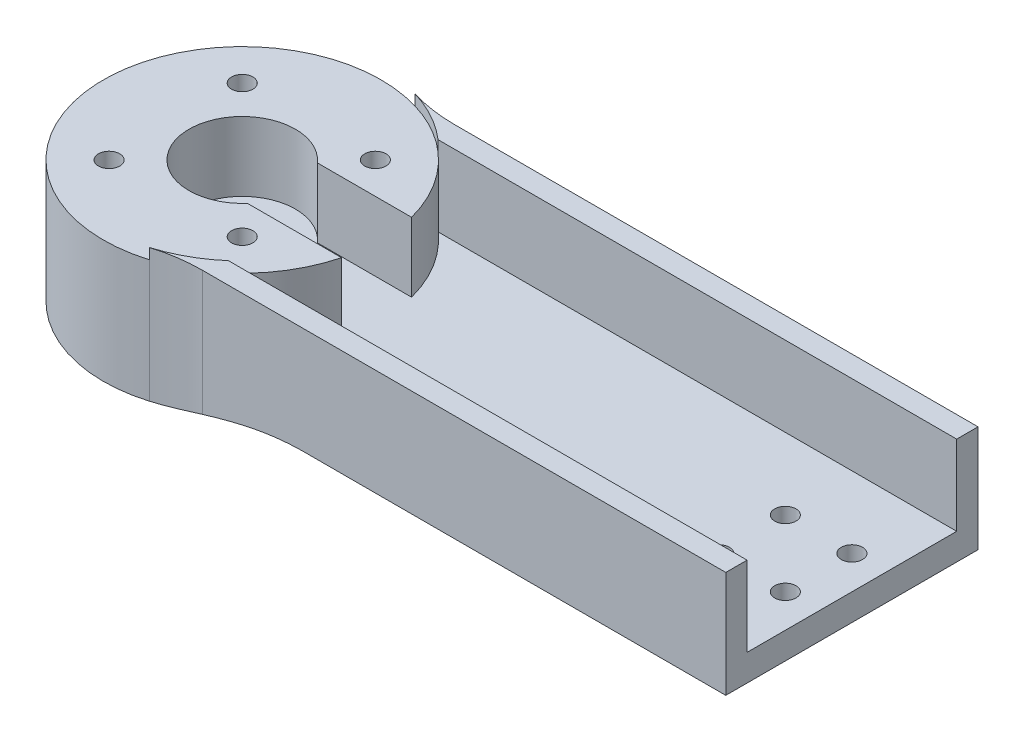
SolidWorks part; units mm, degrees
ref_plane "Front Plane" through (0, 0, 0) normal (0, 0, 1) x (1, 0, 0)
ref_plane "Top Plane" through (0, 0, 0) normal (0, 1, 0) x (1, 0, 0)
ref_plane "Right Plane" through (0, 0, 0) normal (1, 0, 0) x (0, 0, -1)
sketch "Sketch1" plane through (0, 0, 0) normal (0, 1, 0) x (1, 0, 0)
  line L1 (-50.3006, 19.6842) -> (50.3006, 19.6842)
  line L3 (-50.3006, -19.6842) -> (50.3006, -19.6842)
  line L5 (-50.3006, 19.6842) -> (50.3006, -19.6842) construction
  line L6 (-50.3006, -19.6842) -> (50.3006, 19.6842) construction
  line L9 (44.9237, -17.58) -> (39.4721, -17.58)
  line L11 (-50.3006, 0) -> (35, 0) construction
  line L12 (35, 0) -> (43.9443, 0) construction
  line L13 (39.4721, 0) -> (39.4721, -17.58) construction
  line L14 (39.4721, -8.79) -> (28.2221, -8.79) construction
  line L15 (50.3006, 19.6842) -> (50.3006, -19.6842)
  line L16 (-50.3006, 19.6842) -> (-50.3006, -19.6842) construction
  circle A0 centre (33.8471, -8.79) radius 2
  circle A1 centre (45.0971, -8.79) radius 2
  circle A2 centre (45.0971, 8.79) radius 2
  circle A3 centre (33.8471, 8.79) radius 2
  arc A6 (-50.3006, 19.6842) -> (-50.3006, -19.6842) centre (-61.1994, 0) ccw
  point P0 (0, 0)
  point P25 (-83.6994, 0)
  point P26 (50.3006, 0)
  dimension "D3" = 134
  dimension "D4" = 11.25
  dimension "D1" = 45
  dimension "D2" = 5.2035
extrude "Boss-Extrude2" add sketch "Sketch1" along normal blind 5
sketch "Sketch8" plane through (0, 5, 0) normal (0, 1, 0) x (1, 0, 0)
  line L0 (-50.3006, -19.6842) -> (50.3006, -19.6842) construction
  line L1 (-50.3006, 19.6842) -> (50.3006, 19.6842) construction
  line L2 (-50.3006, -19.6842) -> (50.3006, -19.6842)
  line L3 (-50.3006, 19.6842) -> (50.3006, 19.6842)
  line L4 (-50.3006, 23.6842) -> (50.3006, 23.6842)
  line L5 (-50.3006, -23.6842) -> (50.3006, -23.6842)
  line L6 (50.3006, 23.6842) -> (50.3006, 19.6842)
  line L7 (50.3006, -19.6842) -> (50.3006, -23.6842)
  line L8 (-50.3006, -19.6842) -> (-50.3006, -23.6842)
  line L9 (-50.3006, 23.6842) -> (-50.3006, 19.6842)
  dimension "D1" = 4
  dimension "D2" = 4
extrude "Boss-Extrude8" add sketch "Sketch8" along normal blind 15 and the other way up to surface other way up to face at (33.8471, 0, -6.79)
sketch "Sketch9" plane through (0, 5, 0) normal (0, 1, 0) x (1, 0, 0)
  circle A0 centre (-61.1994, 0) radius 26.0715
extrude "Boss-Extrude9" add sketch "Sketch9" along normal blind 15 and the other way blind 10
fillet "Fillet2" radius 30 3 edges at (-35.1279, 0, 0) (-50.3006, 10, -23.6842) (-50.3006, 10, 23.6842)
sketch "Sketch10" plane through (50.3006, 0, 0) normal (1, 0, 0) x (0, 0, -1)
  line L0 (-23.6842, 20) -> (-19.6842, 20) construction
  line L1 (-19.6842, 5) -> (-19.6842, 20) construction
  line L2 (19.6842, 5) -> (-19.6842, 5) construction
  line L3 (19.6842, 5) -> (19.6842, 20) construction
  line L4 (19.6842, 20) -> (23.6842, 20) construction
  line L5 (23.6842, 0) -> (23.6842, 20) construction
  line L6 (23.6842, 0) -> (-23.6842, 0) construction
  line L7 (-23.6842, 20) -> (-23.6842, -3.4498) construction
  line L8 (-23.6842, 20) -> (-19.6842, 20)
  line L9 (-19.6842, 5) -> (-19.6842, 20)
  line L10 (19.6842, 5) -> (-19.6842, 5)
  line L11 (19.6842, 5) -> (19.6842, 20)
  line L12 (19.6842, 20) -> (23.6842, 20)
  line L13 (23.6842, 0) -> (23.6842, 20)
  line L14 (23.6842, 0) -> (-23.6842, 0)
  line L15 (-23.6842, 20) -> (-23.6842, 0)
extrude "Boss-Extrude10" add sketch "Sketch10" along normal blind 3
sketch "Sketch11" plane through (0, 20, 0) normal (0, 1, 0) x (1, 0, 0)
  line L0 (-21.1994, 6.5745) -> (-53.6644, 6.5745)
  line L1 (-61.1994, 0) -> (0, 0) construction
  line L2 (-21.1994, -6.5745) -> (-53.6644, -6.5745)
  line L3 (-21.1994, 6.5745) -> (-21.1994, -6.5745)
  arc A0 (-53.6644, 6.5745) -> (-53.6644, -6.5745) centre (-61.1994, 0) ccw
  dimension "D1" = 40
  dimension "D2" = 20
extrude "Cut-Extrude3" cut sketch "Sketch11" against normal up to surface (15 mm away) up to face at (6.8424, 5, 0)
sketch "Sketch12" plane through (0, 20, 0) normal (0, 1, 0) x (1, 0, 0)
  line L5 (-73.6994, 12.5) -> (-48.6994, -12.5) construction
  line L6 (-73.6994, -12.5) -> (-48.6994, 12.5) construction
  line L7 (-73.6994, 12.5) -> (-48.6994, 12.5) construction
  line L9 (-73.6994, -12.5) -> (-48.6994, -12.5) construction
  line L10 (-48.6994, 12.5) -> (-48.6994, -12.5) construction
  line L11 (-73.6994, 12.5) -> (-48.6994, -12.5) construction
  line L12 (-73.6994, -12.5) -> (-48.6994, 12.5) construction
  circle A0 centre (-48.6994, 12.5) radius 2
  circle A1 centre (-48.6994, -12.5) radius 2
  circle A3 centre (-73.6994, 12.5) radius 2
  circle A4 centre (-73.6994, -12.5) radius 2
  point P0 (-61.1994, 0)
  point P9 (-61.1994, 0)
  dimension "D3" = 25
  dimension "D1" = 25
  dimension "D2" = 25
  dimension "D4" = 25
extrude "Cut-Extrude4" cut sketch "Sketch12" against normal through all
ref_plane "Plane2" through (0, 30, 0) normal (0, 1, 0) x (1, 0, 0)
sketch "Sketch13" plane through (0, 5, 0) normal (0, 1, 0) x (1, 0, 0)
  circle A0 centre (33.8471, -8.79) radius 2 construction
  circle A1 centre (45.0971, -8.79) radius 2 construction
  circle A2 centre (45.0971, 8.79) radius 2 construction
  circle A3 centre (33.8471, 8.79) radius 2 construction
  circle A4 centre (33.8471, -8.79) radius 2
  circle A5 centre (45.0971, -8.79) radius 2
  circle A6 centre (45.0971, 8.79) radius 2
  circle A7 centre (33.8471, 8.79) radius 2
extrude "Boss-Extrude11" add sketch "Sketch13" against normal up to surface (5 mm away) up to face at (33.8471, 0, -6.79)
sketch "Sketch14" plane through (0, 5, 0) normal (0, 1, 0) x (1, 0, 0)
  line L0 (53.3006, 0) -> (0, 0) construction
  line L1 (53.3006, 19.6842) -> (53.3006, -19.6842) construction
  line L2 (40.8006, 12.5) -> (40.8006, 0) construction
  line L3 (28.3006, 12.5) -> (53.3006, 12.5) construction
  line L4 (28.3006, 12.5) -> (28.3006, -12.5) construction
  line L5 (28.3006, -12.5) -> (53.3006, -12.5) construction
  line L6 (53.3006, 12.5) -> (53.3006, -12.5) construction
  line L7 (40.8006, 6.25) -> (28.3006, 6.25) construction
  circle A0 centre (34.5506, 6.25) radius 2
  circle A1 centre (47.0506, 6.25) radius 2
  circle A2 centre (47.0506, -6.25) radius 2
  circle A3 centre (34.5506, -6.25) radius 2
  dimension "D1" = 25
  dimension "D2" = 25
extrude "Cut-Extrude5" cut sketch "Sketch14" against normal through all
sketch "Sketch16" plane through (0, 20, 0) normal (0, 1, 0) x (1, 0, 0)
  circle A0 centre (-61.1994, 0) radius 26.0715
extrude "Cut-Extrude6" cut sketch "Sketch16" against normal blind 2
